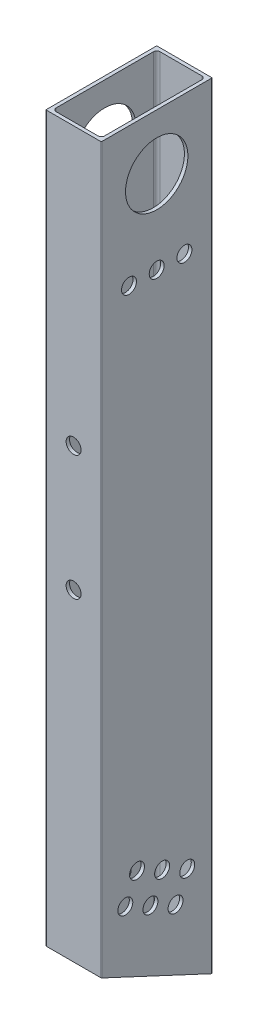
SolidWorks part; units mm, degrees
ref_plane "Front Plane" through (0, 0, 0) normal (0, 0, 1) x (1, 0, 0)
ref_plane "Top Plane" through (0, 0, 0) normal (0, 1, 0) x (1, 0, 0)
ref_plane "Right Plane" through (0, 0, 0) normal (1, 0, 0) x (0, 0, -1)
sketch "Sketch1" plane through (0, 0, 0) normal (0, 1, 0) x (1, 0, 0)
  line L0 (-9.5885, 23.8125) -> (9.5885, 23.8125)
  line L1 (-12.446, -25.4) -> (12.446, -25.4)
  line L2 (-12.7, -25.146) -> (-12.7, 25.146)
  line L3 (-12.446, 25.4) -> (12.446, 25.4)
  line L4 (12.7, -25.146) -> (12.7, 25.146)
  line L5 (-12.7, -25.4) -> (12.7, 25.4) construction
  line L6 (-12.7, 25.4) -> (12.7, -25.4) construction
  line L7 (11.1125, -22.2885) -> (11.1125, 22.2885)
  line L8 (-9.5885, -23.8125) -> (9.5885, -23.8125)
  line L9 (-11.1125, -22.2885) -> (-11.1125, 22.2885)
  line L10 (-11.1125, -23.8125) -> (-11.1125, 23.8125) construction
  line L11 (-11.1125, -23.8125) -> (11.1125, -23.8125) construction
  line L12 (11.1125, -23.8125) -> (11.1125, 23.8125) construction
  line L13 (-11.1125, 23.8125) -> (11.1125, 23.8125) construction
  arc A0 (-12.446, -25.4) -> (-12.7, -25.146) centre (-12.446, -25.146) cw
  arc A1 (12.446, -25.4) -> (12.7, -25.146) centre (12.446, -25.146) ccw
  arc A2 (12.446, 25.4) -> (12.7, 25.146) centre (12.446, 25.146) cw
  arc A3 (-12.7, 25.146) -> (-12.446, 25.4) centre (-12.446, 25.146) cw
  arc A8 (-11.1125, -22.2885) -> (-9.5885, -23.8125) centre (-9.5885, -22.2885) ccw
  arc A9 (-11.1125, -23.8125) -> (-11.1125, -23.8125) centre (-11.1125, -23.8125) cw construction
  arc A10 (9.5885, -23.8125) -> (11.1125, -22.2885) centre (9.5885, -22.2885) ccw
  arc A11 (11.1125, -23.8125) -> (11.1125, -23.8125) centre (11.1125, -23.8125) ccw construction
  arc A12 (11.1125, 22.2885) -> (9.5885, 23.8125) centre (9.5885, 22.2885) ccw
  arc A13 (11.1125, 23.8125) -> (11.1125, 23.8125) centre (11.1125, 23.8125) cw construction
  arc A14 (-11.1125, 22.2885) -> (-9.5885, 23.8125) centre (-9.5885, 22.2885) cw
  arc A15 (-11.1125, 23.8125) -> (-11.1125, 23.8125) centre (-11.1125, 23.8125) cw construction
  point P0 (0, 0)
  dimension "D3" = 0.254
  dimension "D5" = 1.524
  dimension "D1" = 50.8
  dimension "D2" = 25.4
  dimension "D4" = 1.5875
extrude "Boss-Extrude1" add sketch "Sketch1" along normal blind 355.6
sketch "Sketch2" plane through (-12.7, 0, 0) normal (-1, 0, 0) x (0, 0, 1)
  line L1 (0, 355.6) -> (0, 0) construction
  line L2 (-25.146, 355.6) -> (25.146, 355.6) construction
  line L3 (13.97, 0) -> (-13.97, 0) construction
  line L4 (-25.4, 0) -> (25.4, 23.6884)
  line L5 (-25.4, 355.6) -> (-25.4, 0) construction
  line L6 (25.4, 355.6) -> (25.4, 0) construction
  line L7 (25.4, 23.6884) -> (25.4, 0)
  line L8 (-8.6326, 35.8446) -> (0, 39.87) construction
  line L9 (25.4, 0) -> (-25.4, 0)
  line L10 (-12.7, 292.1) -> (12.7, 292.1) construction
  circle A0 centre (-8.6326, 35.8446) radius 3.429
  circle A1 centre (0, 330.2) radius 14.2875
  circle A2 centre (0, 292.1) radius 3.429
  circle A3 centre (12.7, 292.1) radius 3.429
  circle A4 centre (-12.7, 292.1) radius 3.429
  circle A5 centre (2.8775, 41.2118) radius 3.429
  circle A6 centre (14.3876, 46.5791) radius 3.429
  circle A7 centre (-2.4897, 52.7219) radius 3.429
  circle A8 centre (9.0204, 58.0892) radius 3.429
  circle A9 centre (-13.9998, 47.3547) radius 3.429
  point P25 (0, 292.1)
  dimension "D1" = 6.858
  dimension "D2" = 25.4
  dimension "D4" = 25.4
  dimension "D5" = 28.575
  dimension "D6" = 38.1
  dimension "D9" = 3
  dimension "D10" = 2
  dimension "D7" = 12.7
  dimension "D11" = 12.7
  dimension "D3" = 65
  dimension "D8" = 25.4
  dimension "D12" = 9.525
extrude "Cut-Extrude1" cut sketch "Sketch2" against normal through all
sketch "Sketch3" plane through (0, 0, 0) normal (0, 0, 1) x (1, 0, 0)
  line L0 (0, -27.94) -> (0, 27.94) construction
  line L1 (-12.446, 355.6) -> (12.446, 355.6) construction
  circle A0 centre (0, 228.6) radius 3.429
  circle A1 centre (0, 171.45) radius 3.429
  circle A2 centre (0, 228.6) radius 9.525
  circle A3 centre (0, 171.45) radius 9.525
  dimension "D1" = 6.858
  dimension "D2" = 57.15
  dimension "D3" = 127
  dimension "D4" = 19.05
extrude "Cut-Extrude2" cut sketch "Sketch3" along normal through all contours A0 | A1
extrude "Cut-Extrude3" cut sketch "Sketch3<3>" against normal through all contours A2 | A3
sketch "Sketch3<3>" plane through (0, 0, 0) normal (0, 0, 1) x (1, 0, 0) same geometry as "Sketch3"
